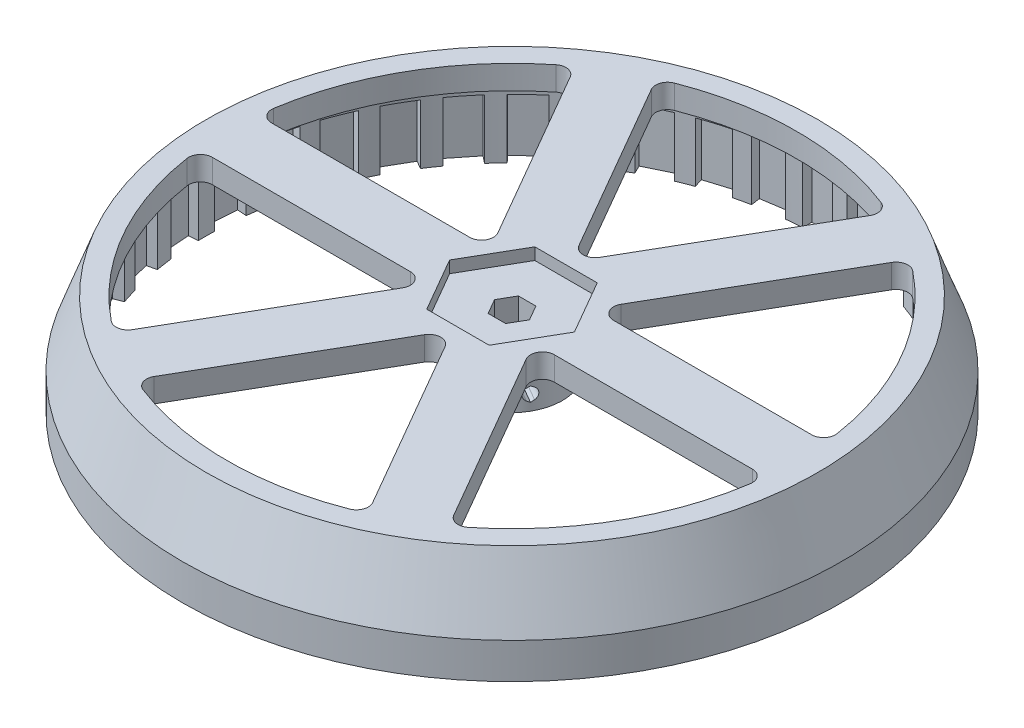
SolidWorks part; units mm, degrees
material "ABS"
ref_plane "Front Plane" through (0, 0, 0) normal (0, 0, 1) x (1, 0, 0)
ref_plane "Top Plane" through (0, 0, 0) normal (0, 1, 0) x (1, 0, 0)
ref_plane "Right Plane" through (0, 0, 0) normal (1, 0, 0) x (0, 0, -1)
sketch "Sketch1" plane through (0, 0, 0) normal (0, 0, 1) x (1, 0, 0)
  line L0 (0, 29) -> (0, 33)
  line L4 (51.5, 29) -> (51.5, 16)
  line L5 (51.5, 16) -> (55.5, 16)
  line L6 (55.5, 16) -> (55.5, 33)
  line L7 (55.5, 33) -> (0, 33)
  line L8 (0, 0) -> (0, 63.0003) construction
  line L11 (0, 29) -> (51.5, 29)
  dimension "D3" = 103
  dimension "D4" = 4
  dimension "D7" = 13
  dimension "D8" = 4
revolve "Main Revolve" add sketch "Sketch1" angle 360 about L8
sketch "Sketch2" plane through (0, 33, 0) normal (0, 1, 0) x (1, 0, 0)
  line L0 (0, 0) -> (0, 75.8468) construction
  line L1 (0, 0) -> (27.75, 48.0644) construction
  line L2 (18.402, 41.8732) -> (1.7321, 13)
  line L3 (-18.402, 41.8732) -> (-1.7321, 13)
  line L4 (0, 0) -> (-27.75, 48.0644) construction
  arc A0 (-17.3947, 44.7373) -> (17.3947, 44.7373) centre (0, 0) cw
  circle A2 centre (0, 0) radius 55.5 construction
  arc A3 (17.3947, 44.7373) -> (18.402, 41.8732) centre (16.67, 42.8732) cw
  arc A6 (-17.3947, 44.7373) -> (-18.402, 41.8732) centre (-16.67, 42.8732) ccw
  arc A8 (1.7321, 13) -> (-1.7321, 13) centre (0, 14) cw
  point P5 (0, 15)
  point P6 (0, 19)
  point P14 (0, 15)
  point P15 (0, 10)
  point P16 (0, 0)
  point P19 (0, 0)
  point P20 (0, 15.3737)
  point P23 (0, 10)
  dimension "D5" = 48
  dimension "D6" = 2
  dimension "D7" = 2
  dimension "D3" = 2
  dimension "D1" = 30
  dimension "D2" = 30
  dimension "D4" = 10
extrude "Slot Cut" cut sketch "Sketch2" against normal through all
pattern_circular "Slot Cut Pattern" count 6 over 360 about axis through (0, 33, 0) along (0, -1, 0) of "Slot Cut"
sketch "Sketch4" plane through (0, 16, 0) normal (0, -1, 0) x (1, 0, 0)
  line L0 (-2.5, 53) -> (2.5, 53)
  line L1 (-2.5, 53) -> (-2.5, 51.4393)
  line L2 (2.5, 53) -> (2.5, 51.4393)
  circle A0 centre (0, 0) radius 51.5 construction
  arc A1 (2.5, 51.4393) -> (-2.5, 51.4393) centre (0, 0) ccw
  point P3 (0, 53)
  dimension "D2" = 1.5
  dimension "D1" = 5
extrude "Magnet Slots" cut sketch "Sketch4" against normal blind 10
pattern_circular "Magnet Cut Pattern" count 42 over 360 about axis through (0, 16, 0) along (0, -1, 0) of "Magnet Slots"
chamfer "Chamfer1" distance 4 angle 70 1 edges at (0, 33, -55.5) first distance on face at (0, 33, 33.6578)
sketch "Sketch5" plane through (0, 33, 0) normal (0, 1, 0) x (1, 0, 0)
  line L1 (2.9445, 0) -> (1.4722, 2.55)
  line L2 (1.4722, 2.55) -> (-1.4722, 2.55)
  line L3 (-1.4722, 2.55) -> (-2.9445, 0)
  line L4 (-2.9445, 0) -> (-1.4722, -2.55)
  line L5 (-1.4722, -2.55) -> (1.4722, -2.55)
  line L6 (1.4722, -2.55) -> (2.9445, 0)
  circle A0 centre (0, 0) radius 2.55 construction
  dimension "D1" = 5.1
extrude "Cut-Extrude1" cut sketch "Sketch5" against normal through all both and the other way through all
sketch "Sketch8" plane through (0, 29, 0) normal (0, -1, 0) x (1, 0, 0)
  line L0 (-1.4722, 2.55) -> (1.4722, 2.55) construction
  line L1 (2.9445, 0) -> (1.4722, 2.55)
  line L2 (1.4722, 2.55) -> (-1.4722, 2.55)
  line L3 (-1.4722, 2.55) -> (-2.9445, 0)
  line L4 (-2.9445, 0) -> (-1.4722, -2.55)
  line L5 (-1.4722, -2.55) -> (1.4722, -2.55)
  line L6 (1.4722, -2.55) -> (2.9445, 0)
  circle A0 centre (0, 0) radius 2.55 construction
  circle A1 centre (0, 0) radius 8.5
  dimension "D1" = 17
extrude "Boss-Extrude1" add sketch "Sketch8" along normal blind 7
sketch "Sketch9" plane through (0, 29, 0) normal (0, -1, 0) x (1, 0, 0)
  circle A0 centre (0, 0) radius 8.5
  circle A1 centre (0, 0) radius 9
  circle A2 centre (0, 0) radius 8.5 construction
  dimension "D1" = 0.5
extrude "Boss-Extrude2" add sketch "Sketch9" along normal blind 1
sketch "Sketch10" plane through (-2.2084, 0, -1.275) normal (0.866, 0, 0.5) x (0.5, 0, -0.866)
  line L0 (0, 27) -> (0, 22) construction
  line L2 (-1.4722, 22) -> (1.4722, 22) construction
  line L4 (2, 27) -> (-2, 27)
  line L5 (2, 27) -> (2, 22)
  line L6 (2, 22) -> (-2, 22)
  line L7 (-2, 27) -> (-2, 22)
  line L8 (2, 27) -> (-2, 22) construction
  line L9 (2, 22) -> (-2, 27) construction
  point P2 (0.1749, 29.0747)
  point P3 (0, 22)
  point P6 (0, 24.5)
  point P11 (0, 0)
  point P12 (0, 22)
  point P13 (2, 22)
  point P14 (0, 0)
  point P15 (-2, 22)
  point P16 (0, 0)
  point P17 (0, 0)
  point P18 (0, 0)
  dimension "D1" = 4
  dimension "D2" = 5
extrude "Cut-Extrude2" cut sketch "Sketch10" against normal blind 1.5 and the other way blind 1
extrude "Cut-Extrude3" cut sketch "Sketch10<2>" along normal blind 1.5 and the other way blind 1.5 from surface starting at face at (2.2084, 27.5, 1.275)
sketch "Sketch10<2>" plane through (-2.2084, 0, -1.275) normal (0.866, 0, 0.5) x (0.5, 0, -0.866) same geometry as "Sketch10"
fillet "Fillet1" radius 0.5 4 edges at (-0.4167, 24.5, -2.55) (2.4167, 24.5, -0.9141) (0.4167, 24.5, 2.55) (-2.4167, 24.5, 0.9141)
sketch "Sketch11" plane through (-3.5074, 0, -2.025) normal (0.866, 0, 0.5) x (0.5, 0, -0.866)
  line L0 (0, 27) -> (0, 22) construction
  line L1 (2, 27) -> (-2, 27) construction
  line L2 (-2, 22) -> (2, 22) construction
  line L3 (0, 24.5) -> (0, 23.3) construction
  line L4 (0, 23.3) -> (-0.5083, 23.5812)
  line L5 (0, 23.3) -> (0.5083, 23.5813)
  line L6 (0, 24.5) -> (0.5997, 24.5) construction
  line L7 (0, 25.7) -> (-0.5083, 25.4188)
  line L8 (0, 25.7) -> (0.5083, 25.4187)
  arc A0 (-0.5083, 25.4188) -> (-0.5083, 23.5812) centre (0, 24.5) ccw
  arc A1 (0.5083, 23.5813) -> (0.5083, 25.4187) centre (0, 24.5) ccw
  dimension "D1" = 2.1
  dimension "D2" = 1.2
extrude "Cut-Extrude4" cut sketch "Sketch11" against normal up to next and the other way blind 15.5 contours L7 A0 L4 L5 A1 L8
sketch "Sketch14" plane through (0, 33, 0) normal (0, 1, 0) x (1, 0, 0)
  line L0 (2.9445, 0) -> (1.4722, 2.55) construction
  line L1 (5.2539, -9.1) -> (10.5078, 0)
  line L2 (10.5078, 0) -> (5.2539, 9.1)
  line L3 (5.2539, 9.1) -> (-5.2539, 9.1)
  line L4 (-5.2539, 9.1) -> (-10.5078, 0)
  line L5 (-10.5078, 0) -> (-5.2539, -9.1)
  line L6 (-5.2539, -9.1) -> (5.2539, -9.1)
  circle A3 centre (0, 0) radius 9.1 construction
  point P12 (9.4783, 0)
  dimension "D1" = 18.2
extrude "Cut-Extrude6" cut sketch "Sketch14" against normal blind 2
equation "\"D3@Sketch1\"=100+2*(1+0.5)"
